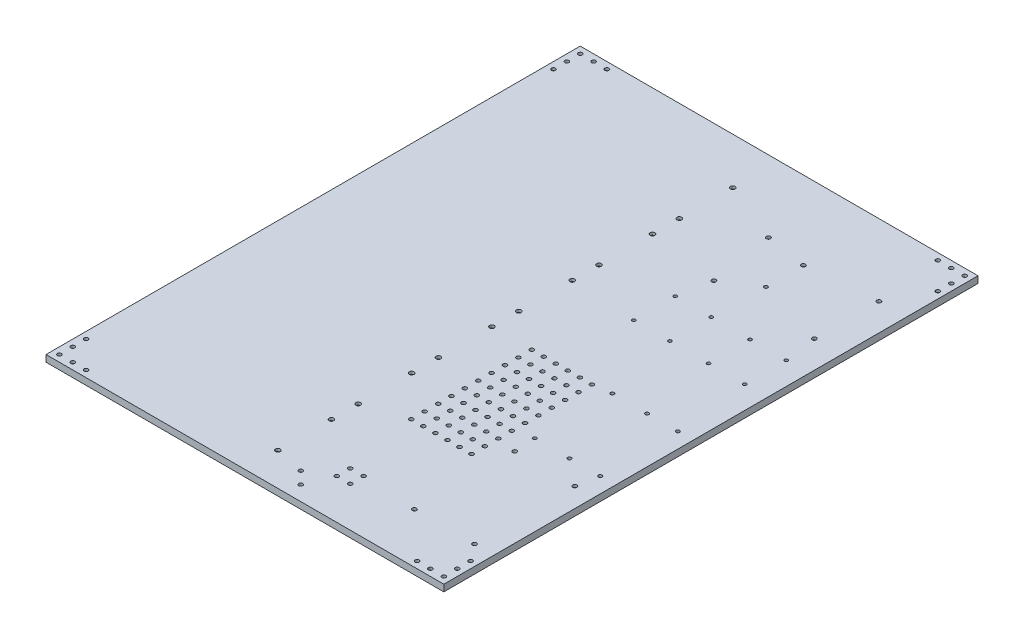
SolidWorks part; units mm, degrees
ref_plane "Front Plane" through (0, 0, 0) normal (0, 0, 1) x (1, 0, 0)
ref_plane "Top Plane" through (0, 0, 0) normal (0, 1, 0) x (1, 0, 0)
ref_plane "Right Plane" through (0, 0, 0) normal (1, 0, 0) x (0, 0, -1)
sketch "Sketch1" plane through (0, 0, 0) normal (0, 1, 0) x (1, 0, 0)
  line L1 (0, 0) -> (297.5, 0)
  line L2 (0, 0) -> (0, 399.5)
  line L3 (0, 399.5) -> (297.5, 399.5)
  line L4 (297.5, 0) -> (297.5, 399.5)
  dimension "D1" = 399.5
  dimension "D2" = 297.5
extrude "Boss-Extrude1" add sketch "Sketch1" along normal blind 5
sketch "Sketch3" plane through (0, 5, 0) normal (0, 1, 0) x (1, 0, 0)
  circle A0 centre (148.7481, 24.6847) radius 1.7499
  circle A1 centre (148.7483, 64.6837) radius 1.7504
  circle A2 centre (148.7504, 84.7207) radius 1.7502
  circle A3 centre (148.748, 124.721) radius 1.7496
  circle A4 centre (148.749, 144.7501) radius 1.751
  circle A5 centre (148.7475, 184.7526) radius 1.7486
  circle A6 centre (148.747, 204.7868) radius 1.7489
  circle A7 centre (148.7482, 244.7868) radius 1.7499
  circle A8 centre (148.747, 264.8168) radius 1.7489
  circle A9 centre (148.7502, 304.8159) radius 1.751
  circle A10 centre (148.747, 324.8528) radius 1.7489
  circle A11 centre (148.751, 364.8529) radius 1.7522
extrude "Cut-Extrude2" cut sketch "Sketch3" against normal blind 10
sketch "Sketch5" plane through (0, 5, 0) normal (0, 1, 0) x (1, 0, 0)
  line L0 (0, 0) -> (297.5, 0) construction
  line L1 (10, 10) -> (287.5, 10)
  line L2 (10, 10) -> (10, 389.5)
  line L3 (10, 389.5) -> (287.5, 389.5)
  line L4 (287.5, 10) -> (287.5, 389.5)
  line L5 (0, 399.5) -> (0, 0) construction
  line L6 (297.5, 399.5) -> (0, 399.5) construction
  line L7 (297.5, 0) -> (297.5, 399.5) construction
  line L8 (0, 199.75) -> (297.5, 199.75)
  line L9 (148.75, 0) -> (148.75, 399.5)
  circle A0 centre (5, 5) radius 1.5
  circle A1 centre (5, 15) radius 1.5
  circle A2 centre (15, 5) radius 1.5
  circle A3 centre (5, 25) radius 1.5
  circle A4 centre (25, 5) radius 1.5
  circle A5 centre (25, 394.5) radius 1.5
  circle A6 centre (15, 394.5) radius 1.5
  circle A7 centre (5, 374.5) radius 1.5
  circle A8 centre (5, 384.5) radius 1.5
  circle A9 centre (5, 394.5) radius 1.5
  circle A10 centre (292.5, 374.5) radius 1.5
  circle A11 centre (292.5, 384.5) radius 1.5
  circle A12 centre (292.5, 394.5) radius 1.5
  circle A13 centre (282.5, 394.5) radius 1.5
  circle A14 centre (272.5, 394.5) radius 1.5
  circle A15 centre (292.5, 25) radius 1.5
  circle A16 centre (292.5, 15) radius 1.5
  circle A17 centre (292.5, 5) radius 1.5
  circle A18 centre (282.5, 5) radius 1.5
  circle A19 centre (272.5, 5) radius 1.5
  dimension "D5" = 3
  dimension "D6" = 5
  dimension "D7" = 5
  dimension "D8" = 3
  dimension "D9" = 3
  dimension "D10" = 3
  dimension "D11" = 3
  dimension "D12" = 5
  dimension "D13" = 5
  dimension "D14" = 5
  dimension "D15" = 5
  dimension "D16" = 10
  dimension "D17" = 10
  dimension "D18" = 10
  dimension "D19" = 10
  dimension "D1" = 10
  dimension "D2" = 10
  dimension "D3" = 10
  dimension "D4" = 10
extrude "Cut-Extrude3" cut sketch "Sketch5" against normal blind 10 contours A19 | A18 | A17 | A16 | A15 | A10 | A11 | A12 | A13 | A14 | A7 | A8 | A9 | A6 | A5 | A4 | A2 | A0 | A1 | A3 region at (5, 5, -5) region at (5, 5, -15) region at (15, 5, -5) region at (5, 5, -25) region at (25, 5, -5) region at (25, 5, -394.5) region at (15, 5, -394.5) region at (5, 5, -374.5) region at (5, 5, -384.5) region at (5, 5, -394.5) region at (292.5, 5, -374.5) region at (292.5, 5, -384.5) region at (292.5, 5, -394.5) region at (282.5, 5, -394.5) region at (272.5, 5, -394.5) region at (292.5, 5, -25) region at (292.5, 5, -15) region at (292.5, 5, -5) region at (282.5, 5, -5) region at (272.5, 5, -5)
sketch "Sketch6" plane through (0, 0, 0) normal (0, -1, 0) x (1, 0, 0)
  line L0 (0, -199.75) -> (297.5, -199.75)
  line L1 (1.2091, -394.5) -> (3.1046, -397.783)
  line L2 (3.1046, -397.783) -> (6.8954, -397.783)
  line L3 (6.8954, -397.783) -> (8.7909, -394.5)
  line L4 (8.7909, -394.5) -> (6.8954, -391.217)
  line L5 (6.8954, -391.217) -> (3.1046, -391.217)
  line L6 (3.1046, -391.217) -> (1.2091, -394.5)
  line L7 (1.2091, -384.5) -> (3.1046, -387.783)
  line L8 (3.1046, -387.783) -> (6.8954, -387.783)
  line L9 (6.8954, -387.783) -> (8.7909, -384.5)
  line L10 (8.7909, -384.5) -> (6.8954, -381.217)
  line L11 (6.8954, -381.217) -> (3.1046, -381.217)
  line L12 (3.1046, -381.217) -> (1.2091, -384.5)
  line L13 (1.2091, -374.5) -> (3.1046, -377.783)
  line L14 (3.1046, -377.783) -> (6.8954, -377.783)
  line L15 (6.8954, -377.783) -> (8.7909, -374.5)
  line L16 (8.7909, -374.5) -> (6.8954, -371.217)
  line L17 (6.8954, -371.217) -> (3.1046, -371.217)
  line L18 (3.1046, -371.217) -> (1.2091, -374.5)
  line L19 (11.2091, -394.5) -> (13.1046, -397.783)
  line L20 (13.1046, -397.783) -> (16.8954, -397.783)
  line L21 (16.8954, -397.783) -> (18.7909, -394.5)
  line L22 (18.7909, -394.5) -> (16.8954, -391.217)
  line L23 (16.8954, -391.217) -> (13.1046, -391.217)
  line L24 (13.1046, -391.217) -> (11.2091, -394.5)
  line L25 (21.2091, -394.5) -> (23.1046, -397.783)
  line L26 (23.1046, -397.783) -> (26.8954, -397.783)
  line L27 (26.8954, -397.783) -> (28.7909, -394.5)
  line L28 (28.7909, -394.5) -> (26.8954, -391.217)
  line L29 (26.8954, -391.217) -> (23.1046, -391.217)
  line L30 (23.1046, -391.217) -> (21.2091, -394.5)
  line L31 (0, -399.5) -> (0, 0) construction
  line L32 (297.5, 0) -> (297.5, -399.5) construction
  line L33 (3.1046, -28.283) -> (1.2091, -25)
  line L34 (6.8954, -28.283) -> (3.1046, -28.283)
  line L35 (8.7909, -25) -> (6.8954, -28.283)
  line L36 (6.8954, -21.717) -> (8.7909, -25)
  line L37 (3.1046, -21.717) -> (6.8954, -21.717)
  line L38 (1.2091, -25) -> (3.1046, -21.717)
  line L39 (3.1046, -18.283) -> (1.2091, -15)
  line L40 (6.8954, -18.283) -> (3.1046, -18.283)
  line L41 (8.7909, -15) -> (6.8954, -18.283)
  line L42 (6.8954, -11.717) -> (8.7909, -15)
  line L43 (3.1046, -11.717) -> (6.8954, -11.717)
  line L44 (1.2091, -15) -> (3.1046, -11.717)
  line L45 (3.1046, -8.283) -> (1.2091, -5)
  line L46 (6.8954, -8.283) -> (3.1046, -8.283)
  line L47 (8.7909, -5) -> (6.8954, -8.283)
  line L48 (6.8954, -1.717) -> (8.7909, -5)
  line L49 (3.1046, -1.717) -> (6.8954, -1.717)
  line L50 (1.2091, -5) -> (3.1046, -1.717)
  line L51 (13.1046, -8.283) -> (11.2091, -5)
  line L52 (16.8954, -8.283) -> (13.1046, -8.283)
  line L53 (18.7909, -5) -> (16.8954, -8.283)
  line L54 (16.8954, -1.717) -> (18.7909, -5)
  line L55 (13.1046, -1.717) -> (16.8954, -1.717)
  line L56 (11.2091, -5) -> (13.1046, -1.717)
  line L57 (23.1046, -8.283) -> (21.2091, -5)
  line L58 (26.8954, -8.283) -> (23.1046, -8.283)
  line L59 (28.7909, -5) -> (26.8954, -8.283)
  line L60 (26.8954, -1.717) -> (28.7909, -5)
  line L61 (23.1046, -1.717) -> (26.8954, -1.717)
  line L62 (21.2091, -5) -> (23.1046, -1.717)
  line L63 (148.75, -399.5) -> (148.75, 0)
  line L64 (297.5, -399.5) -> (0, -399.5) construction
  line L65 (0, 0) -> (297.5, 0) construction
  line L66 (270.6046, -8.283) -> (274.3954, -8.283)
  line L67 (268.7091, -5) -> (270.6046, -8.283)
  line L68 (270.6046, -1.717) -> (268.7091, -5)
  line L69 (274.3954, -1.717) -> (270.6046, -1.717)
  line L70 (276.2909, -5) -> (274.3954, -1.717)
  line L71 (274.3954, -8.283) -> (276.2909, -5)
  line L72 (280.6046, -8.283) -> (284.3954, -8.283)
  line L73 (278.7091, -5) -> (280.6046, -8.283)
  line L74 (280.6046, -1.717) -> (278.7091, -5)
  line L75 (284.3954, -1.717) -> (280.6046, -1.717)
  line L76 (286.2909, -5) -> (284.3954, -1.717)
  line L77 (284.3954, -8.283) -> (286.2909, -5)
  line L78 (290.6046, -8.283) -> (294.3954, -8.283)
  line L79 (288.7091, -5) -> (290.6046, -8.283)
  line L80 (290.6046, -1.717) -> (288.7091, -5)
  line L81 (294.3954, -1.717) -> (290.6046, -1.717)
  line L82 (296.2909, -5) -> (294.3954, -1.717)
  line L83 (294.3954, -8.283) -> (296.2909, -5)
  line L84 (290.6046, -18.283) -> (294.3954, -18.283)
  line L85 (288.7091, -15) -> (290.6046, -18.283)
  line L86 (290.6046, -11.717) -> (288.7091, -15)
  line L87 (294.3954, -11.717) -> (290.6046, -11.717)
  line L88 (296.2909, -15) -> (294.3954, -11.717)
  line L89 (294.3954, -18.283) -> (296.2909, -15)
  line L90 (290.6046, -28.283) -> (294.3954, -28.283)
  line L91 (288.7091, -25) -> (290.6046, -28.283)
  line L92 (290.6046, -21.717) -> (288.7091, -25)
  line L93 (294.3954, -21.717) -> (290.6046, -21.717)
  line L94 (296.2909, -25) -> (294.3954, -21.717)
  line L95 (294.3954, -28.283) -> (296.2909, -25)
  line L96 (294.3954, -371.217) -> (296.2909, -374.5)
  line L97 (290.6046, -371.217) -> (294.3954, -371.217)
  line L98 (288.7091, -374.5) -> (290.6046, -371.217)
  line L99 (290.6046, -377.783) -> (288.7091, -374.5)
  line L100 (294.3954, -377.783) -> (290.6046, -377.783)
  line L101 (296.2909, -374.5) -> (294.3954, -377.783)
  line L102 (294.3954, -381.217) -> (296.2909, -384.5)
  line L103 (290.6046, -381.217) -> (294.3954, -381.217)
  line L104 (288.7091, -384.5) -> (290.6046, -381.217)
  line L105 (290.6046, -387.783) -> (288.7091, -384.5)
  line L106 (294.3954, -387.783) -> (290.6046, -387.783)
  line L107 (296.2909, -384.5) -> (294.3954, -387.783)
  line L108 (294.3954, -391.217) -> (296.2909, -394.5)
  line L109 (290.6046, -391.217) -> (294.3954, -391.217)
  line L110 (288.7091, -394.5) -> (290.6046, -391.217)
  line L111 (290.6046, -397.783) -> (288.7091, -394.5)
  line L112 (294.3954, -397.783) -> (290.6046, -397.783)
  line L113 (296.2909, -394.5) -> (294.3954, -397.783)
  line L114 (284.3954, -391.217) -> (286.2909, -394.5)
  line L115 (280.6046, -391.217) -> (284.3954, -391.217)
  line L116 (278.7091, -394.5) -> (280.6046, -391.217)
  line L117 (280.6046, -397.783) -> (278.7091, -394.5)
  line L118 (284.3954, -397.783) -> (280.6046, -397.783)
  line L119 (286.2909, -394.5) -> (284.3954, -397.783)
  line L120 (274.3954, -391.217) -> (276.2909, -394.5)
  line L121 (270.6046, -391.217) -> (274.3954, -391.217)
  line L122 (268.7091, -394.5) -> (270.6046, -391.217)
  line L123 (270.6046, -397.783) -> (268.7091, -394.5)
  line L124 (274.3954, -397.783) -> (270.6046, -397.783)
  line L125 (276.2909, -394.5) -> (274.3954, -397.783)
  circle A0 centre (5, -394.5) radius 3.283 construction
  circle A1 centre (5, -384.5) radius 3.283 construction
  circle A2 centre (5, -374.5) radius 3.283 construction
  circle A3 centre (15, -394.5) radius 3.283 construction
  circle A4 centre (25, -394.5) radius 3.283 construction
  circle M63 centre (282.5, -5) radius 1.5
  circle M64 centre (292.5, -5) radius 1.5
  circle M65 centre (292.5, -15) radius 1.5
  circle M66 centre (292.5, -25) radius 1.5
  circle M67 centre (25, -394.5) radius 1.5
  circle M68 centre (15, -394.5) radius 1.5
  circle M69 centre (5, -374.5) radius 1.5
  circle M70 centre (5, -384.5) radius 1.5
  circle M71 centre (5, -394.5) radius 1.5
  circle M72 centre (272.5, -5) radius 1.5
  circle M89 centre (5, -25) radius 1.5
  circle M90 centre (5, -15) radius 1.5
  circle M91 centre (5, -5) radius 1.5
  circle M92 centre (272.5, -394.5) radius 1.5
  circle M93 centre (25, -5) radius 1.5
  circle M94 centre (15, -5) radius 1.5
  circle M95 centre (282.5, -394.5) radius 1.5
  circle M96 centre (292.5, -394.5) radius 1.5
  circle M97 centre (292.5, -384.5) radius 1.5
  circle M98 centre (292.5, -374.5) radius 1.5
  dimension "D1" = 7.5818
  dimension "D2" = 7.5818
  dimension "D3" = 7.5818
  dimension "D4" = 7.5818
  dimension "D5" = 7.5818
extrude "Cut-Extrude4" cut sketch "Sketch6" against normal blind 3 contours L119 L114 L115 L116 L117 L118 M95 | L125 L120 L121 L122 L123 L124 M92 | L113 L108 L109 L110 L111 L112 M96 | L107 L102 L103 L104 L105 L106 M97 | L101 L96 L97 L98 L99 L100 M98 | L5 L6 L1 L2 L3 L4 M71 | L23 L24 L19 L20 L21 L22 M68 | L29 L30 L25 L26 L27 L28 M67 | L11 L12 L7 L8 L9 L10 M70 | L17 L18 L13 L14 L15 L16 M69 | L38 L33 L34 L35 L36 L37 M89 | L44 L39 L40 L41 L42 L43 M90 | L50 L45 L46 L47 L48 L49 M91 | L56 L51 L52 L53 L54 L55 M94 | L62 L57 L58 L59 L60 L61 M93 | L66 L71 L70 L69 L68 L67 M72 | L72 L77 L76 L75 L74 L73 M63 | L78 L83 L82 L81 L80 L79 M64 | L84 L89 L88 L87 L86 L85 M65 | L90 L95 L94 L93 L92 L91 M66 region at (2.2437, 0, -392.9086) region at (2.2437, 0, -382.9086) region at (2.2437, 0, -372.9086) region at (12.2437, 0, -392.9086) region at (22.2437, 0, -392.9086) region at (2.2437, 0, -26.5914) region at (2.2437, 0, -16.5914) region at (2.2437, 0, -6.5914) region at (12.2437, 0, -6.5914) region at (22.2437, 0, -6.5914) region at (269.7437, 0, -6.5914) region at (279.7437, 0, -6.5914) region at (289.7437, 0, -6.5914) region at (289.7437, 0, -16.5914) region at (289.7437, 0, -26.5914) region at (295.2563, 0, -372.9086) region at (295.2563, 0, -382.9086) region at (295.2563, 0, -392.9086) region at (285.2563, 0, -392.9086) region at (275.2563, 0, -392.9086)
sketch "Sketch7" plane through (0, 0, 0) normal (0, -1, 0) x (1, 0, 0)
  line L1 (152.5419, -364.8529) -> (150.6465, -361.5698)
  line L2 (150.6465, -361.5698) -> (146.8556, -361.5698)
  line L3 (146.8556, -361.5698) -> (144.9601, -364.8529)
  line L4 (144.9601, -364.8529) -> (146.8556, -368.1359)
  line L5 (146.8556, -368.1359) -> (150.6465, -368.1359)
  line L6 (150.6465, -368.1359) -> (152.5419, -364.8529)
  line L7 (152.5379, -324.8528) -> (150.6425, -321.5698)
  line L8 (150.6425, -321.5698) -> (146.8516, -321.5698)
  line L9 (146.8516, -321.5698) -> (144.9561, -324.8528)
  line L10 (144.9561, -324.8528) -> (146.8516, -328.1358)
  line L11 (146.8516, -328.1358) -> (150.6425, -328.1358)
  line L12 (150.6425, -328.1358) -> (152.5379, -324.8528)
  line L13 (152.5411, -304.8159) -> (150.6457, -301.5328)
  line L14 (150.6457, -301.5328) -> (146.8548, -301.5328)
  line L15 (146.8548, -301.5328) -> (144.9593, -304.8159)
  line L16 (144.9593, -304.8159) -> (146.8548, -308.0989)
  line L17 (146.8548, -308.0989) -> (150.6457, -308.0989)
  line L18 (150.6457, -308.0989) -> (152.5411, -304.8159)
  line L19 (152.5379, -264.8168) -> (150.6424, -261.5338)
  line L20 (150.6424, -261.5338) -> (146.8516, -261.5338)
  line L21 (146.8516, -261.5338) -> (144.9561, -264.8168)
  line L22 (144.9561, -264.8168) -> (146.8516, -268.0999)
  line L23 (146.8516, -268.0999) -> (150.6424, -268.0999)
  line L24 (150.6424, -268.0999) -> (152.5379, -264.8168)
  line L25 (152.5391, -244.7868) -> (150.6437, -241.5038)
  line L26 (150.6437, -241.5038) -> (146.8528, -241.5038)
  line L27 (146.8528, -241.5038) -> (144.9573, -244.7868)
  line L28 (144.9573, -244.7868) -> (146.8528, -248.0698)
  line L29 (146.8528, -248.0698) -> (150.6437, -248.0698)
  line L30 (150.6437, -248.0698) -> (152.5391, -244.7868)
  line L31 (152.539, -24.6847) -> (150.6435, -21.4017)
  line L32 (150.6435, -21.4017) -> (146.8526, -21.4017)
  line L33 (146.8526, -21.4017) -> (144.9572, -24.6847)
  line L34 (144.9572, -24.6847) -> (146.8526, -27.9678)
  line L35 (146.8526, -27.9678) -> (150.6435, -27.9678)
  line L36 (150.6435, -27.9678) -> (152.539, -24.6847)
  line L37 (152.5392, -64.6837) -> (150.6438, -61.4007)
  line L38 (150.6438, -61.4007) -> (146.8529, -61.4007)
  line L39 (146.8529, -61.4007) -> (144.9574, -64.6837)
  line L40 (144.9574, -64.6837) -> (146.8529, -67.9667)
  line L41 (146.8529, -67.9667) -> (150.6438, -67.9667)
  line L42 (150.6438, -67.9667) -> (152.5392, -64.6837)
  line L43 (152.5413, -84.7207) -> (150.6459, -81.4377)
  line L44 (150.6459, -81.4377) -> (146.855, -81.4377)
  line L45 (146.855, -81.4377) -> (144.9595, -84.7207)
  line L46 (144.9595, -84.7207) -> (146.855, -88.0037)
  line L47 (146.855, -88.0037) -> (150.6459, -88.0037)
  line L48 (150.6459, -88.0037) -> (152.5413, -84.7207)
  line L49 (152.5389, -124.721) -> (150.6435, -121.438)
  line L50 (150.6435, -121.438) -> (146.8526, -121.438)
  line L51 (146.8526, -121.438) -> (144.9571, -124.721)
  line L52 (144.9571, -124.721) -> (146.8526, -128.004)
  line L53 (146.8526, -128.004) -> (150.6435, -128.004)
  line L54 (150.6435, -128.004) -> (152.5389, -124.721)
  line L55 (152.5399, -144.7501) -> (150.6445, -141.4671)
  line L56 (150.6445, -141.4671) -> (146.8536, -141.4671)
  line L57 (146.8536, -141.4671) -> (144.9581, -144.7501)
  line L58 (144.9581, -144.7501) -> (146.8536, -148.0331)
  line L59 (146.8536, -148.0331) -> (150.6445, -148.0331)
  line L60 (150.6445, -148.0331) -> (152.5399, -144.7501)
  line L61 (152.5384, -184.7526) -> (150.643, -181.4696)
  line L62 (150.643, -181.4696) -> (146.8521, -181.4696)
  line L63 (146.8521, -181.4696) -> (144.9566, -184.7526)
  line L64 (144.9566, -184.7526) -> (146.8521, -188.0356)
  line L65 (146.8521, -188.0356) -> (150.643, -188.0356)
  line L66 (150.643, -188.0356) -> (152.5384, -184.7526)
  line L67 (152.5379, -204.7868) -> (150.6425, -201.5038)
  line L68 (150.6425, -201.5038) -> (146.8516, -201.5038)
  line L69 (146.8516, -201.5038) -> (144.9561, -204.7868)
  line L70 (144.9561, -204.7868) -> (146.8516, -208.0698)
  line L71 (146.8516, -208.0698) -> (150.6425, -208.0698)
  line L72 (150.6425, -208.0698) -> (152.5379, -204.7868)
  circle A0 centre (148.751, -364.8529) radius 3.283 construction
  circle A1 centre (148.747, -324.8528) radius 3.283 construction
  circle A2 centre (148.7502, -304.8159) radius 3.283 construction
  circle A3 centre (148.747, -264.8168) radius 3.283 construction
  circle A4 centre (148.7482, -244.7868) radius 3.283 construction
  circle A5 centre (148.7481, -24.6847) radius 3.283 construction
  circle A6 centre (148.7483, -64.6837) radius 3.283 construction
  circle A7 centre (148.7504, -84.7207) radius 3.283 construction
  circle A8 centre (148.748, -124.721) radius 3.283 construction
  circle A9 centre (148.749, -144.7501) radius 3.283 construction
  circle A10 centre (148.7475, -184.7526) radius 3.283 construction
  circle A11 centre (148.747, -204.7868) radius 3.283 construction
  dimension "D1" = 7.5818
  dimension "D2" = 7.5818
  dimension "D3" = 7.5818
  dimension "D4" = 7.5818
  dimension "D5" = 7.5818
  dimension "D6" = 7.5818
  dimension "D7" = 7.5818
  dimension "D8" = 7.5818
  dimension "D9" = 7.5818
  dimension "D10" = 7.5818
  dimension "D11" = 7.5818
  dimension "D12" = 7.5818
extrude "Cut-Extrude5" cut sketch "Sketch7" against normal blind 3
sketch "Sketch13" plane through (0, 5, 0) normal (0, 1, 0) x (1, 0, 0)
  line L0 (0, 0) -> (297.5, 0) construction
  line L1 (297.5, 0) -> (297.5, 399.5) construction
  circle A0 centre (170.5, 20) radius 1.5
  circle A1 centre (179.5, 11) radius 1.5
  dimension "D1" = 3
  dimension "D2" = 3
  dimension "D3" = 11
  dimension "D4" = 118
  dimension "D5" = 127
  dimension "D6" = 20
extrude "Cut-Extrude6" cut sketch "Sketch13" against normal blind 5
sketch "Sketch14" plane through (0, 0, 0) normal (0, -1, 0) x (1, 0, 0)
  line L1 (181.5249, -14.2048) -> (183.2879, -10.8488)
  line L2 (183.2879, -10.8488) -> (181.263, -7.644)
  line L3 (181.263, -7.644) -> (177.4751, -7.7952)
  line L4 (177.4751, -7.7952) -> (175.7121, -11.1512)
  line L5 (175.7121, -11.1512) -> (177.737, -14.356)
  line L6 (177.737, -14.356) -> (181.5249, -14.2048)
  line L7 (172.5249, -23.2048) -> (174.2879, -19.8488)
  line L8 (174.2879, -19.8488) -> (172.263, -16.644)
  line L9 (172.263, -16.644) -> (168.4751, -16.7952)
  line L10 (168.4751, -16.7952) -> (166.7121, -20.1512)
  line L11 (166.7121, -20.1512) -> (168.737, -23.356)
  line L12 (168.737, -23.356) -> (172.5249, -23.2048)
  circle A0 centre (179.5, -11) radius 3.283 construction
  circle A1 centre (170.5, -20) radius 3.283 construction
  dimension "D1" = 7.5818
  dimension "D2" = 7.5818
extrude "Cut-Extrude7" cut sketch "Sketch14" against normal blind 3
sketch "Sketch15" plane through (0, 5, 0) normal (0, 1, 0) x (1, 0, 0)
  line L0 (0, 0) -> (297.5, 0) construction
  line L1 (297.5, 0) -> (297.5, 399.5) construction
  circle A0 centre (187.5, 30) radius 1.5
  circle A1 centre (197.5, 30) radius 1.5
  circle A2 centre (187.5, 40) radius 1.5
  circle A3 centre (197.5, 40) radius 1.5
  dimension "D1" = 3
  dimension "D2" = 3
  dimension "D3" = 3
  dimension "D4" = 3
  dimension "D5" = 30
  dimension "D6" = 30
  dimension "D7" = 10
  dimension "D8" = 10
  dimension "D9" = 10
  dimension "D10" = 10
  dimension "D11" = 100
extrude "Cut-Extrude8" cut sketch "Sketch15" against normal blind 10
sketch "Sketch16" plane through (0, 0, 0) normal (0, -1, 0) x (1, 0, 0)
  line L1 (191.29, -30) -> (189.395, -26.7178)
  line L2 (189.395, -26.7178) -> (185.605, -26.7178)
  line L3 (185.605, -26.7178) -> (183.71, -30)
  line L4 (183.71, -30) -> (185.605, -33.2822)
  line L5 (185.605, -33.2822) -> (189.395, -33.2822)
  line L6 (189.395, -33.2822) -> (191.29, -30)
  line L7 (201.29, -30) -> (199.395, -26.7178)
  line L8 (199.395, -26.7178) -> (195.605, -26.7178)
  line L9 (195.605, -26.7178) -> (193.71, -30)
  line L10 (193.71, -30) -> (195.605, -33.2822)
  line L11 (195.605, -33.2822) -> (199.395, -33.2822)
  line L12 (199.395, -33.2822) -> (201.29, -30)
  line L13 (201.29, -40) -> (199.395, -36.7178)
  line L14 (199.395, -36.7178) -> (195.605, -36.7178)
  line L15 (195.605, -36.7178) -> (193.71, -40)
  line L16 (193.71, -40) -> (195.605, -43.2822)
  line L17 (195.605, -43.2822) -> (199.395, -43.2822)
  line L18 (199.395, -43.2822) -> (201.29, -40)
  line L19 (191.29, -40) -> (189.395, -36.7178)
  line L20 (189.395, -36.7178) -> (185.605, -36.7178)
  line L21 (185.605, -36.7178) -> (183.71, -40)
  line L22 (183.71, -40) -> (185.605, -43.2822)
  line L23 (185.605, -43.2822) -> (189.395, -43.2822)
  line L24 (189.395, -43.2822) -> (191.29, -40)
  circle A0 centre (187.5, -30) radius 3.2822 construction
  circle A1 centre (197.5, -30) radius 3.2822 construction
  circle A2 centre (197.5, -40) radius 3.2822 construction
  circle A3 centre (187.5, -40) radius 3.2822 construction
  dimension "D1" = 7.58
  dimension "D2" = 7.58
  dimension "D3" = 7.58
  dimension "D4" = 7.58
extrude "Cut-Extrude9" cut sketch "Sketch16" against normal blind 3
sketch "Sketch21" plane through (0, 5, 0) normal (0, 1, 0) x (1, 0, 0)
  circle A0 centre (238, 112.5) radius 1.5508 construction
  circle A1 centre (238, 37.5) radius 1.5508 construction
  circle A2 centre (283, 37.5) radius 1.5508 construction
  circle A3 centre (283, 112.5) radius 1.5508 construction
  circle A4 centre (238, 112.5) radius 1.5508
  circle A5 centre (238, 37.5) radius 1.5508
  circle A6 centre (283, 37.5) radius 1.5508
  circle A7 centre (283, 112.5) radius 1.5508
  circle A8 centre (201.8944, 297.54) radius 1.5621 construction
  circle A9 centre (194.4014, 345.8762) radius 1.5621 construction
  circle A10 centre (225.4021, 312.9815) radius 1.3153 construction
  circle A11 centre (225.4021, 340.9977) radius 1.5621 construction
  circle A12 centre (277.0276, 345.8762) radius 1.5621 construction
  circle A13 centre (277.0276, 297.54) radius 1.5621 construction
  arc A14 (196.25, 273) -> (198.75, 273) centre (197.5, 273) ccw construction
  arc A15 (198.75, 273) -> (196.25, 273) centre (197.5, 273) ccw construction
  arc A16 (223.25, 273) -> (225.75, 273) centre (224.5, 273) ccw construction
  arc A17 (225.75, 273) -> (223.25, 273) centre (224.5, 273) ccw construction
  arc A18 (225.75, 242) -> (223.25, 242) centre (224.5, 242) ccw construction
  arc A19 (223.25, 242) -> (225.75, 242) centre (224.5, 242) ccw construction
  arc A20 (196.25, 242) -> (198.75, 242) centre (197.5, 242) ccw construction
  arc A21 (198.75, 242) -> (196.25, 242) centre (197.5, 242) ccw construction
  arc A22 (254.75, 273) -> (252.25, 273) centre (253.5, 273) ccw construction
  arc A23 (252.25, 273) -> (254.75, 273) centre (253.5, 273) ccw construction
  arc A24 (279.25, 273) -> (281.75, 273) centre (280.5, 273) ccw construction
  arc A25 (281.75, 273) -> (279.25, 273) centre (280.5, 273) ccw construction
  arc A26 (281.75, 242) -> (279.25, 242) centre (280.5, 242) ccw construction
  arc A27 (279.25, 242) -> (281.75, 242) centre (280.5, 242) ccw construction
  arc A28 (252.25, 242) -> (254.75, 242) centre (253.5, 242) ccw construction
  arc A29 (254.75, 242) -> (252.25, 242) centre (253.5, 242) ccw construction
  arc A30 (287.35, 128.5) -> (284.65, 128.5) centre (286, 128.5) ccw construction
  arc A31 (284.65, 128.5) -> (287.35, 128.5) centre (286, 128.5) ccw construction
  arc A32 (284.65, 186.5) -> (287.35, 186.5) centre (286, 186.5) ccw construction
  arc A33 (287.35, 186.5) -> (284.65, 186.5) centre (286, 186.5) ccw construction
  arc A34 (261.65, 186.5) -> (264.35, 186.5) centre (263, 186.5) ccw construction
  arc A35 (264.35, 186.5) -> (261.65, 186.5) centre (263, 186.5) ccw construction
  arc A36 (261.65, 128.5) -> (264.35, 128.5) centre (263, 128.5) ccw construction
  arc A37 (264.35, 128.5) -> (261.65, 128.5) centre (263, 128.5) ccw construction
  arc A38 (235.65, 128.5) -> (238.35, 128.5) centre (237, 128.5) ccw construction
  arc A39 (238.35, 128.5) -> (235.65, 128.5) centre (237, 128.5) ccw construction
  circle A40 centre (201.8944, 297.54) radius 1.5621
  circle A41 centre (194.4014, 345.8762) radius 1.5621
  circle A42 centre (225.4021, 312.9815) radius 1.3153
  circle A43 centre (225.4021, 340.9977) radius 1.5621
  circle A44 centre (277.0276, 345.8762) radius 1.5621
  circle A45 centre (277.0276, 297.54) radius 1.5621
  arc A46 (196.25, 273) -> (198.75, 273) centre (197.5, 273) ccw
  arc A47 (198.75, 273) -> (196.25, 273) centre (197.5, 273) ccw
  arc A48 (223.25, 273) -> (225.75, 273) centre (224.5, 273) ccw
  arc A49 (225.75, 273) -> (223.25, 273) centre (224.5, 273) ccw
  arc A50 (225.75, 242) -> (223.25, 242) centre (224.5, 242) ccw
  arc A51 (223.25, 242) -> (225.75, 242) centre (224.5, 242) ccw
  arc A52 (196.25, 242) -> (198.75, 242) centre (197.5, 242) ccw
  arc A53 (198.75, 242) -> (196.25, 242) centre (197.5, 242) ccw
  arc A54 (254.75, 273) -> (252.25, 273) centre (253.5, 273) ccw
  arc A55 (252.25, 273) -> (254.75, 273) centre (253.5, 273) ccw
  arc A56 (279.25, 273) -> (281.75, 273) centre (280.5, 273) ccw
  arc A57 (281.75, 273) -> (279.25, 273) centre (280.5, 273) ccw
  arc A58 (281.75, 242) -> (279.25, 242) centre (280.5, 242) ccw
  arc A59 (279.25, 242) -> (281.75, 242) centre (280.5, 242) ccw
  arc A60 (252.25, 242) -> (254.75, 242) centre (253.5, 242) ccw
  arc A61 (254.75, 242) -> (252.25, 242) centre (253.5, 242) ccw
  arc A62 (287.35, 128.5) -> (284.65, 128.5) centre (286, 128.5) ccw
  arc A63 (284.65, 128.5) -> (287.35, 128.5) centre (286, 128.5) ccw
  arc A64 (284.65, 186.5) -> (287.35, 186.5) centre (286, 186.5) ccw
  arc A65 (287.35, 186.5) -> (284.65, 186.5) centre (286, 186.5) ccw
  arc A66 (261.65, 186.5) -> (264.35, 186.5) centre (263, 186.5) ccw
  arc A67 (264.35, 186.5) -> (261.65, 186.5) centre (263, 186.5) ccw
  arc A68 (261.65, 128.5) -> (264.35, 128.5) centre (263, 128.5) ccw
  arc A69 (264.35, 128.5) -> (261.65, 128.5) centre (263, 128.5) ccw
  arc A70 (235.65, 128.5) -> (238.35, 128.5) centre (237, 128.5) ccw
  arc A71 (238.35, 128.5) -> (235.65, 128.5) centre (237, 128.5) ccw
extrude "Cut-Extrude10" cut sketch "Sketch21" against normal blind 10
sketch "Sketch22" plane through (0, 5, 0) normal (0, 1, 0) x (1, 0, 0)
  circle A0 centre (178.5252, 184.7018) radius 1.5
  circle A1 centre (178.5252, 174.7018) radius 1.5
  circle A2 centre (178.5252, 164.7018) radius 1.5
  circle A3 centre (178.5252, 154.7018) radius 1.5
  circle A4 centre (178.5252, 144.7018) radius 1.5
  circle A5 centre (178.5252, 134.7018) radius 1.5
  circle A6 centre (178.5252, 124.7018) radius 1.5
  circle A7 centre (178.5252, 114.7018) radius 1.5
  circle A8 centre (178.5252, 104.7018) radius 1.5
  circle A9 centre (178.5252, 94.7018) radius 1.5
  circle A10 centre (187.5252, 174.7018) radius 1.5
  circle A11 centre (187.5252, 164.7018) radius 1.5
  circle A12 centre (187.5252, 154.7018) radius 1.5
  circle A13 centre (187.5252, 144.7018) radius 1.5
  circle A14 centre (187.5252, 134.7018) radius 1.5
  circle A15 centre (187.5252, 124.7018) radius 1.5
  circle A16 centre (187.5252, 114.7018) radius 1.5
  circle A17 centre (187.5252, 104.7018) radius 1.5
  circle A18 centre (187.5252, 94.7018) radius 1.5
  circle A19 centre (196.5252, 174.7018) radius 1.5
  circle A20 centre (196.5252, 164.7018) radius 1.5
  circle A21 centre (196.5252, 154.7018) radius 1.5
  circle A22 centre (196.5252, 144.7018) radius 1.5
  circle A23 centre (196.5252, 134.7018) radius 1.5
  circle A24 centre (196.5252, 124.7018) radius 1.5
  circle A25 centre (196.5252, 114.7018) radius 1.5
  circle A26 centre (196.5252, 104.7018) radius 1.5
  circle A27 centre (196.5252, 94.7018) radius 1.5
  circle A28 centre (205.5252, 174.7018) radius 1.5
  circle A29 centre (205.5252, 164.7018) radius 1.5
  circle A30 centre (205.5252, 154.7018) radius 1.5
  circle A31 centre (205.5252, 144.7018) radius 1.5
  circle A32 centre (205.5252, 134.7018) radius 1.5
  circle A33 centre (205.5252, 124.7018) radius 1.5
  circle A34 centre (205.5252, 114.7018) radius 1.5
  circle A35 centre (205.5252, 104.7018) radius 1.5
  circle A36 centre (205.5252, 94.7018) radius 1.5
  circle A37 centre (214.5252, 174.7018) radius 1.5
  circle A38 centre (214.5252, 164.7018) radius 1.5
  circle A39 centre (214.5252, 154.7018) radius 1.5
  circle A40 centre (214.5252, 144.7018) radius 1.5
  circle A41 centre (214.5252, 134.7018) radius 1.5
  circle A42 centre (214.5252, 124.7018) radius 1.5
  circle A43 centre (214.5252, 114.7018) radius 1.5
  circle A44 centre (214.5252, 104.7018) radius 1.5
  circle A45 centre (214.5252, 94.7018) radius 1.5
  circle A46 centre (223.5252, 174.7018) radius 1.5
  circle A47 centre (223.5252, 164.7018) radius 1.5
  circle A48 centre (223.5252, 154.7018) radius 1.5
  circle A49 centre (223.5252, 144.7018) radius 1.5
  circle A50 centre (223.5252, 134.7018) radius 1.5
  circle A51 centre (223.5252, 124.7018) radius 1.5
  circle A52 centre (223.5252, 114.7018) radius 1.5
  circle A53 centre (223.5252, 104.7018) radius 1.5
  circle A54 centre (223.5252, 94.7018) radius 1.5
  circle A55 centre (187.5252, 184.7018) radius 1.5
  circle A56 centre (196.5252, 184.7018) radius 1.5
  circle A57 centre (205.5252, 184.7018) radius 1.5
  circle A58 centre (214.5252, 184.7018) radius 1.5
  circle A59 centre (223.5252, 184.7018) radius 1.5
  dimension "D3" = 3
  dimension "D4" = 10
  dimension "D5" = 9
  dimension "D1" = 10
  dimension "D2" = 6
extrude "Cut-Extrude11" cut sketch "Sketch22" against normal blind 10
sketch "Sketch23" plane through (0, 0, 0) normal (0, -1, 0) x (1, 0, 0)
  circle A0 centre (283, -37.5) radius 3 construction
  circle A1 centre (283, -37.5) radius 3
  circle A2 centre (283, -37.5) radius 4.5
  circle A3 centre (238, -37.5) radius 4.5
  circle A4 centre (238, -112.5) radius 4.5
  circle A5 centre (283, -112.5) radius 4.5
  dimension "D1" = 9
  dimension "D2" = 9
  dimension "D3" = 9
  dimension "D4" = 9
extrude "Cut-Extrude12" cut sketch "Sketch23" against normal blind 3 contours A1 | A2 A1 | A3 | A5 | A4 region at (283, 0, -37.5) region at (278.6273, 0, -37.5) region at (238, 0, -37.5) region at (238, 0, -112.5) region at (283, 0, -112.5)
sketch "Sketch24" plane through (0, 5, 0) normal (0, 1, 0) x (1, 0, 0)
  arc A0 (238.35, 186.5) -> (235.65, 186.5) centre (237, 186.5) ccw construction
  arc A1 (235.65, 186.5) -> (238.35, 186.5) centre (237, 186.5) ccw construction
  arc A2 (238.35, 186.5) -> (235.65, 186.5) centre (237, 186.5) ccw
  arc A3 (235.65, 186.5) -> (238.35, 186.5) centre (237, 186.5) ccw
extrude "Cut-Extrude13" cut sketch "Sketch24" against normal blind 5
sketch "Sketch28" plane through (0, 0, 0) normal (0, -1, 0) x (1, 0, 0)
  line L1 (289.79, -128.5) -> (287.895, -125.2178)
  line L2 (287.895, -125.2178) -> (284.105, -125.2178)
  line L3 (284.105, -125.2178) -> (282.21, -128.5)
  line L4 (282.21, -128.5) -> (284.105, -131.7822)
  line L5 (284.105, -131.7822) -> (287.895, -131.7822)
  line L6 (287.895, -131.7822) -> (289.79, -128.5)
  line L7 (266.79, -128.5) -> (264.895, -125.2178)
  line L8 (264.895, -125.2178) -> (261.105, -125.2178)
  line L9 (261.105, -125.2178) -> (259.21, -128.5)
  line L10 (259.21, -128.5) -> (261.105, -131.7822)
  line L11 (261.105, -131.7822) -> (264.895, -131.7822)
  line L12 (264.895, -131.7822) -> (266.79, -128.5)
  line L13 (240.79, -128.5) -> (238.895, -125.2178)
  line L14 (238.895, -125.2178) -> (235.105, -125.2178)
  line L15 (235.105, -125.2178) -> (233.21, -128.5)
  line L16 (233.21, -128.5) -> (235.105, -131.7822)
  line L17 (235.105, -131.7822) -> (238.895, -131.7822)
  line L18 (238.895, -131.7822) -> (240.79, -128.5)
  line L19 (289.79, -186.5) -> (287.895, -183.2178)
  line L20 (287.895, -183.2178) -> (284.105, -183.2178)
  line L21 (284.105, -183.2178) -> (282.21, -186.5)
  line L22 (282.21, -186.5) -> (284.105, -189.7822)
  line L23 (284.105, -189.7822) -> (287.895, -189.7822)
  line L24 (287.895, -189.7822) -> (289.79, -186.5)
  line L25 (266.79, -186.5) -> (264.895, -183.2178)
  line L26 (264.895, -183.2178) -> (261.105, -183.2178)
  line L27 (261.105, -183.2178) -> (259.21, -186.5)
  line L28 (259.21, -186.5) -> (261.105, -189.7822)
  line L29 (261.105, -189.7822) -> (264.895, -189.7822)
  line L30 (264.895, -189.7822) -> (266.79, -186.5)
  line L31 (240.79, -186.5) -> (238.895, -183.2178)
  line L32 (238.895, -183.2178) -> (235.105, -183.2178)
  line L33 (235.105, -183.2178) -> (233.21, -186.5)
  line L34 (233.21, -186.5) -> (235.105, -189.7822)
  line L35 (235.105, -189.7822) -> (238.895, -189.7822)
  line L36 (238.895, -189.7822) -> (240.79, -186.5)
  line L37 (284.29, -242) -> (282.395, -238.7178)
  line L38 (282.395, -238.7178) -> (278.605, -238.7178)
  line L39 (278.605, -238.7178) -> (276.71, -242)
  line L40 (276.71, -242) -> (278.605, -245.2822)
  line L41 (278.605, -245.2822) -> (282.395, -245.2822)
  line L42 (282.395, -245.2822) -> (284.29, -242)
  line L43 (257.29, -242) -> (255.395, -238.7178)
  line L44 (255.395, -238.7178) -> (251.605, -238.7178)
  line L45 (251.605, -238.7178) -> (249.71, -242)
  line L46 (249.71, -242) -> (251.605, -245.2822)
  line L47 (251.605, -245.2822) -> (255.395, -245.2822)
  line L48 (255.395, -245.2822) -> (257.29, -242)
  line L49 (228.29, -242) -> (226.395, -238.7178)
  line L50 (226.395, -238.7178) -> (222.605, -238.7178)
  line L51 (222.605, -238.7178) -> (220.71, -242)
  line L52 (220.71, -242) -> (222.605, -245.2822)
  line L53 (222.605, -245.2822) -> (226.395, -245.2822)
  line L54 (226.395, -245.2822) -> (228.29, -242)
  line L55 (201.29, -242) -> (199.395, -238.7178)
  line L56 (199.395, -238.7178) -> (195.605, -238.7178)
  line L57 (195.605, -238.7178) -> (193.71, -242)
  line L58 (193.71, -242) -> (195.605, -245.2822)
  line L59 (195.605, -245.2822) -> (199.395, -245.2822)
  line L60 (199.395, -245.2822) -> (201.29, -242)
  line L61 (201.29, -273) -> (199.395, -269.7178)
  line L62 (199.395, -269.7178) -> (195.605, -269.7178)
  line L63 (195.605, -269.7178) -> (193.71, -273)
  line L64 (193.71, -273) -> (195.605, -276.2822)
  line L65 (195.605, -276.2822) -> (199.395, -276.2822)
  line L66 (199.395, -276.2822) -> (201.29, -273)
  line L67 (205.6844, -297.54) -> (203.7894, -294.2578)
  line L68 (203.7894, -294.2578) -> (199.9994, -294.2578)
  line L69 (199.9994, -294.2578) -> (198.1044, -297.54)
  line L70 (198.1044, -297.54) -> (199.9994, -300.8222)
  line L71 (199.9994, -300.8222) -> (203.7894, -300.8222)
  line L72 (203.7894, -300.8222) -> (205.6844, -297.54)
  line L73 (198.1914, -345.8762) -> (196.2964, -342.594)
  line L74 (196.2964, -342.594) -> (192.5064, -342.594)
  line L75 (192.5064, -342.594) -> (190.6114, -345.8762)
  line L76 (190.6114, -345.8762) -> (192.5064, -349.1584)
  line L77 (192.5064, -349.1584) -> (196.2964, -349.1584)
  line L78 (196.2964, -349.1584) -> (198.1914, -345.8762)
  line L79 (229.1921, -312.9815) -> (227.2971, -309.6993)
  line L80 (227.2971, -309.6993) -> (223.5071, -309.6993)
  line L81 (223.5071, -309.6993) -> (221.6121, -312.9815)
  line L82 (221.6121, -312.9815) -> (223.5071, -316.2637)
  line L83 (223.5071, -316.2637) -> (227.2971, -316.2637)
  line L84 (227.2971, -316.2637) -> (229.1921, -312.9815)
  line L85 (229.1921, -340.9977) -> (227.2971, -337.7155)
  line L86 (227.2971, -337.7155) -> (223.5071, -337.7155)
  line L87 (223.5071, -337.7155) -> (221.6121, -340.9977)
  line L88 (221.6121, -340.9977) -> (223.5071, -344.2799)
  line L89 (223.5071, -344.2799) -> (227.2971, -344.2799)
  line L90 (227.2971, -344.2799) -> (229.1921, -340.9977)
  line L91 (228.29, -273) -> (226.395, -269.7178)
  line L92 (226.395, -269.7178) -> (222.605, -269.7178)
  line L93 (222.605, -269.7178) -> (220.71, -273)
  line L94 (220.71, -273) -> (222.605, -276.2822)
  line L95 (222.605, -276.2822) -> (226.395, -276.2822)
  line L96 (226.395, -276.2822) -> (228.29, -273)
  line L97 (257.29, -273) -> (255.395, -269.7178)
  line L98 (255.395, -269.7178) -> (251.605, -269.7178)
  line L99 (251.605, -269.7178) -> (249.71, -273)
  line L100 (249.71, -273) -> (251.605, -276.2822)
  line L101 (251.605, -276.2822) -> (255.395, -276.2822)
  line L102 (255.395, -276.2822) -> (257.29, -273)
  line L103 (284.29, -273) -> (282.395, -269.7178)
  line L104 (282.395, -269.7178) -> (278.605, -269.7178)
  line L105 (278.605, -269.7178) -> (276.71, -273)
  line L106 (276.71, -273) -> (278.605, -276.2822)
  line L107 (278.605, -276.2822) -> (282.395, -276.2822)
  line L108 (282.395, -276.2822) -> (284.29, -273)
  line L109 (280.8176, -297.54) -> (278.9226, -294.2578)
  line L110 (278.9226, -294.2578) -> (275.1326, -294.2578)
  line L111 (275.1326, -294.2578) -> (273.2376, -297.54)
  line L112 (273.2376, -297.54) -> (275.1326, -300.8222)
  line L113 (275.1326, -300.8222) -> (278.9226, -300.8222)
  line L114 (278.9226, -300.8222) -> (280.8176, -297.54)
  line L115 (280.8176, -345.8762) -> (278.9226, -342.594)
  line L116 (278.9226, -342.594) -> (275.1326, -342.594)
  line L117 (275.1326, -342.594) -> (273.2376, -345.8762)
  line L118 (273.2376, -345.8762) -> (275.1326, -349.1584)
  line L119 (275.1326, -349.1584) -> (278.9226, -349.1584)
  line L120 (278.9226, -349.1584) -> (280.8176, -345.8762)
  circle A0 centre (286, -128.5) radius 3.2822 construction
  circle A1 centre (263, -128.5) radius 3.2822 construction
  circle A2 centre (237, -128.5) radius 3.2822 construction
  circle A3 centre (286, -186.5) radius 3.2822 construction
  circle A4 centre (263, -186.5) radius 3.2822 construction
  circle A5 centre (237, -186.5) radius 3.2822 construction
  circle A6 centre (280.5, -242) radius 3.2822 construction
  circle A7 centre (253.5, -242) radius 3.2822 construction
  circle A8 centre (224.5, -242) radius 3.2822 construction
  circle A9 centre (197.5, -242) radius 3.2822 construction
  circle A10 centre (197.5, -273) radius 3.2822 construction
  circle A11 centre (201.8944, -297.54) radius 3.2822 construction
  circle A12 centre (194.4014, -345.8762) radius 3.2822 construction
  circle A13 centre (225.4021, -312.9815) radius 3.2822 construction
  circle A14 centre (225.4021, -340.9977) radius 3.2822 construction
  circle A15 centre (224.5, -273) radius 3.2822 construction
  circle A16 centre (253.5, -273) radius 3.2822 construction
  circle A17 centre (280.5, -273) radius 3.2822 construction
  circle A18 centre (277.0276, -297.54) radius 3.2822 construction
  circle A19 centre (277.0276, -345.8762) radius 3.2822 construction
  dimension "D1" = 7.58
  dimension "D2" = 7.58
  dimension "D3" = 7.58
  dimension "D4" = 7.58
  dimension "D5" = 7.58
  dimension "D6" = 7.58
  dimension "D7" = 7.58
  dimension "D8" = 7.58
  dimension "D9" = 7.58
  dimension "D10" = 7.58
  dimension "D11" = 7.58
  dimension "D12" = 7.58
  dimension "D13" = 7.58
  dimension "D14" = 7.58
  dimension "D15" = 7.58
  dimension "D16" = 7.58
  dimension "D17" = 7.58
  dimension "D18" = 7.58
  dimension "D19" = 7.58
  dimension "D20" = 7.58
extrude "Cut-Extrude14" cut sketch "Sketch28" against normal blind 3
